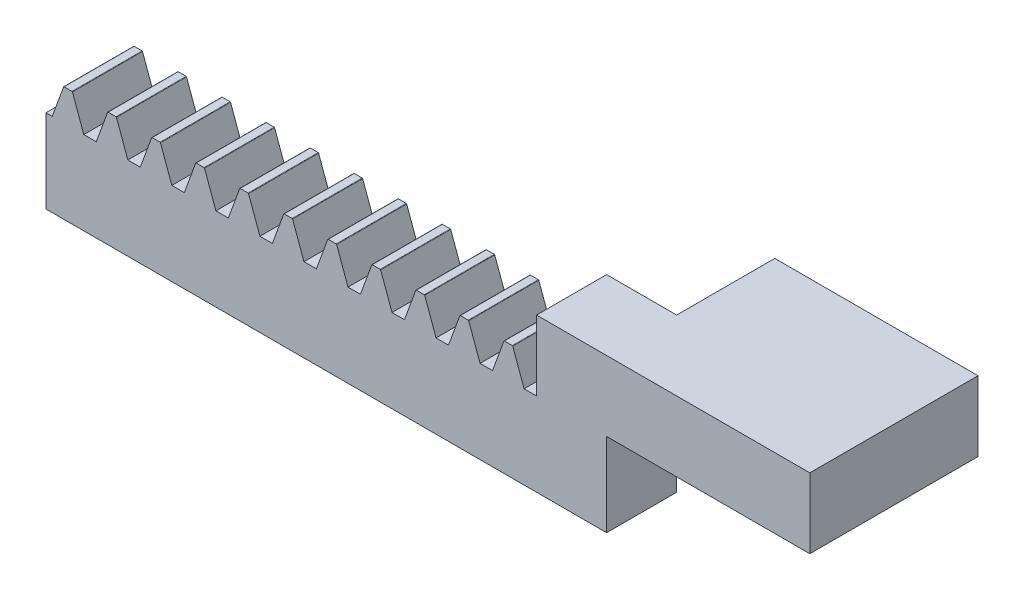
SolidWorks part; units mm, degrees
extrude "Blank" add sketch "BlankSke" against normal blind 5
sketch "BlankSke" plane through (0, 0, 0) normal (0, 0, 1) x (1, 0, 0)
  line L1 (0, 0) -> (40, 0)
  line L2 (0, 0) -> (0, 8.2)
  line L3 (0, 8.2) -> (40, 8.2)
  line L4 (40, 0) -> (40, 8.2)
  dimension "Length" = 40
ref_plane "Plane1" through (0, 0, 0) normal (0, 0, 1) x (1, 0, 0)
ref_plane "Plane2" through (0, 0, 0) normal (0, 1, 0) x (1, 0, 0)
ref_plane "Plane3" through (0, 0, 0) normal (1, 0, 0) x (0, 0, -1)
sketch "HoldingSke" plane through (0, 0, 0) normal (0, 1, 0) x (1, 0, 0)
  line L0 (0, 0) -> (0.1392, 0.9903)
  line L1 (-15, 0) -> (100, 0) construction
  line L2 (0, 0) -> (-2.1039, 2.3779)
  line L3 (0, 0) -> (-11.863, 4.5341)
  line L4 (0, 0) -> (8.3795, 2.0892)
  line L5 (0, 0) -> (-23.7986, -8.8762)
  line L6 (0, 0) -> (-10.5278, -7.1032)
  line L9 (-71.009, 38.7566) -> (-33.4213, 52.4374)
  line L10 (-76.2, 3.3779) -> (-69, 3.3779)
  line L11 (0, 0) -> (-5, 0)
  line L12 (-76.2, 101.6) -> (-76.162, 101.6)
  line L13 (24.9733, 27.94) -> (52.9518, 28.4284)
  line L14 (24.9733, 27.94) -> (24.9743, 27.94)
  line L15 (24.9733, 27.94) -> (100.4006, 29.5858)
  circle A0 centre (0, 0) radius 19.05
  circle A1 centre (0, 0) radius 3.6
  circle A2 centre (0, 0) radius 12.7
  dimension "Num_teeth" = 14
  dimension "Width" = 5
  dimension "Length" = 40
  dimension "Pitch_height" = 7.2
sketch "TooCutSkeIll" plane through (0, 0, 0) normal (0, 0, 1) x (1, 0, 0)
  line L0 (-1.2538, 8.1737) -> (-0.5045, 6.1152)
  line L1 (-0.2687, 5.95) -> (0.2687, 5.95)
  line L2 (0.5045, 6.1152) -> (1.2538, 8.1737)
  line L3 (40, 8.2) -> (0, 8.2) construction
  line L4 (0, 0) -> (0, 64.897) construction
  line L5 (-13.208, 7.2) -> (12.954, 7.2) construction
  line L6 (0, 0) -> (40, 0) construction
  line L7 (0.8994, 7.2) -> (0.8994, 48.7463) construction
  line L8 (-0.8994, 7.2) -> (-0.8994, 48.7463) construction
  line L9 (1.2914, 8.2) -> (1.2914, 8.2254)
  line L10 (-1.2914, 8.2) -> (-1.2914, 8.2254)
  line L11 (-1.2914, 8.2254) -> (1.2914, 8.2254)
  arc A0 (0.2687, 5.95) -> (0.5045, 6.1152) centre (0.2687, 6.201) ccw
  arc A1 (-0.5045, 6.1152) -> (-0.2687, 5.95) centre (-0.2687, 6.201) ccw
  arc A2 (1.2914, 8.2) -> (1.2538, 8.1737) centre (1.2914, 8.16) ccw
  arc A3 (-1.2538, 8.1737) -> (-1.2914, 8.2) centre (-1.2914, 8.16) ccw
  dimension "Addendum_plus" = 1.0254
  dimension "Pitch_height" = 7.2
  dimension "Pressure_angle" = 20
  dimension "Gap_width" = 1.7988
  dimension "Dedendum" = 1.25
extrude "ToothCutIll" cut sketch "TooCutSkeIll" against normal through all
sketch "TooCutSkeSim" plane through (0, 0, 0) normal (0, 0, 1) x (1, 0, 0)
  line L0 (0.4444, 5.95) -> (-0.4444, 5.95)
  line L1 (1.2726, 8.2254) -> (0.4444, 5.95)
  line L2 (0, 17.4625) -> (0, 53.467) construction
  line L3 (1.2726, 8.2254) -> (-1.2726, 8.2254)
  line L6 (-1.2726, 8.2254) -> (-0.4444, 5.95)
  line L9 (-0.8994, 7.2) -> (0.8994, 7.2) construction
  line L10 (0, 0) -> (40, 0) construction
  line L11 (0.8994, 7.2) -> (0.8994, 53.467) construction
  line L12 (-0.8994, 7.2) -> (-0.8994, 53.467) construction
  dimension "Addendum_plus" = 1.0254
  dimension "Pitch_height" = 7.2
  dimension "Pressure_angle" = 20
  dimension "Gap_width" = 1.7988
  dimension "Dedendum" = 1.25
extrude "ToothCutSim" cut sketch "TooCutSkeSim" against normal through all
pattern_linear "TeethCuts" count 14 spacing 3.1416 along (1, 0, 0) of "ToothCutIll", "ToothCutSim"
sketch "Sketch1" plane through (0, 0, 0) normal (0, 0, 1) x (1, 0, 0)
  line L0 (35.002, 5.95) -> (40, 5.95)
  line L1 (40, 0) -> (40, 7.0387) construction
  line L2 (40, 5.95) -> (40, 8.2)
  line L3 (40, 8.2) -> (35.002, 8.2)
  line L4 (35.002, 8.2) -> (35.002, 5.95)
extrude "Boss-Extrude1" add sketch "Sketch1" against normal blind 5
sketch "Sketch3" plane through (0, 0, 0) normal (0, 0, 1) x (1, 0, 0)
  line L1 (35.002, 5.95) -> (40, 5.95)
  line L2 (35.002, 5.95) -> (35.002, 8.2)
  line L3 (35.002, 8.2) -> (40, 8.2)
  line L4 (40, 5.95) -> (40, 8.2)
sketch "Sketch4" plane through (40, 0, 0) normal (1, 0, 0) x (0, 0, -1)
  line L1 (0, 8.2) -> (12, 8.2)
  line L2 (0, 8.2) -> (0, 5.95)
  line L3 (0, 5.95) -> (12, 5.95)
  line L4 (12, 8.2) -> (12, 5.95)
  line L7 (0, 0) -> (0, 8.2) construction
  line L8 (5, 8.2) -> (0, 8.2) construction
  line L9 (0, 0) -> (0, 8.2) construction
  point P4 (0, 0)
  point P5 (0, 8.2)
  point P7 (5.4545, 5.95)
  point P8 (0, 0)
  point P9 (0, 0)
  dimension "D1" = 12
  dimension "D2" = 2.25
extrude "Boss-Extrude4" add sketch "Sketch4" along normal blind 14.5
sketch "Sketch6" plane through (0, 8.2, 0) normal (0, 1, 0) x (1, 0, 0)
  line L10 (35.002, 5) -> (35.002, 0)
  line L24 (35.002, 5) -> (35.002, 0)
  line L34 (40, 5) -> (35.002, 5)
  line L35 (40, 5) -> (35.002, 5)
  line L57 (35.002, 0) -> (54.5, 0)
  line L59 (35.002, 0) -> (54.5, 0)
  line L61 (54.5, 0) -> (54.5, 12)
  line L62 (54.5, 0) -> (54.5, 12)
  line L63 (54.5, 12) -> (40, 12)
  line L64 (54.5, 12) -> (40, 12)
  line L65 (40, 12) -> (40, 5)
  line L66 (40, 12) -> (40, 5)
  dimension "D1" = 0
extrude "Boss-Extrude5" add sketch "Sketch6" along normal blind 2.75
ref_plane "Plane4" through (0, 0, -2.5) normal (0, 0, -1) x (-1, 0, 0)
equation "' \"Module@HoldingSke\" = 6.35"
equation "' \"Num_teeth@HoldingSke\" = 12"
equation "' \"Ap@HoldingSke\" =  20"
equation "' \"Ap@HoldingSke\" = 20"
equation "' \"Width@HoldingSke\" = 0.25 * 25.4"
equation "' \"Show_teeth@HoldingSke\" = 500"
equation "' \"Backlash@HoldingSke\" = 0.009 * 25.4"
equation "' \"Addendum_fac@HoldingSke\" = 1.0"
equation "' \"Dedendum_fac@HoldingSke\" = 1.25"
equation "' \"Dedendum_add@HoldingSke\" = 0.00005 * 25.4"
equation "' \"Clearance_fac@HoldingSke\" = 0.25"
equation "' \"Pitch_height@HoldingSke\" = 1 * 25.4"
equation "' \"Length@HoldingSke\" = 4.71 * 25.4"
equation "\"Pitch@HoldingSke\" = 1 / \"Module@HoldingSke\""
equation "\"MPH@HoldingSke\" = \"Dedendum_fac@HoldingSke\" / \"Pitch@HoldingSke\" + 2 * \"Dedendum_add@HoldingSke\" + 0.002 * 25.4"
equation "\"MPH@HoldingSke\" = ((sgn( \"MPH@HoldingSke\" - \"Pitch_height@HoldingSke\")+1)*( \"MPH@HoldingSke\" - \"Pitch_height@HoldingSke\"))/2 + \"Pitch_height@HoldingSke\""
equation "\"Blank_height@BlankSke\" = \"Pitch_height@HoldingSke\" + \"Addendum_fac@HoldingSke\"  / \"Pitch@HoldingSke\" "
equation "\"Length@BlankSke\" =  \"Length@HoldingSke\""
equation "\"Face_width@Blank\" = \"Width@HoldingSke\""
equation "\"Pressure_angle@TooCutSkeIll\" = \"Ap@HoldingSke\""
equation "\"Addendum_plus@TooCutSkeIll\" =  \"Addendum_fac@HoldingSke\"  / \"Pitch@HoldingSke\" + 0.001 *25.4"
equation "\"Dedendum@TooCutSkeIll\" = \"Dedendum_fac@HoldingSke\"  / \"Pitch@HoldingSke\""
equation "\"Pitch_height@TooCutSkeIll\" =  \"MPH@HoldingSke\""
equation "\"Gap_width@TooCutSkeIll\" = 3.14159265 / 2 / \"Pitch@HoldingSke\" + 6 * \"Backlash@HoldingSke\""
equation "\"Pressure_angle@TooCutSkeSim\" = \"Ap@HoldingSke\""
equation "\"Addendum_plus@TooCutSkeSim\" =  \"Addendum_fac@HoldingSke\"  / \"Pitch@HoldingSke\" + 0.001 * 25.4"
equation "\"Dedendum@TooCutSkeSim\" = \"Dedendum_fac@HoldingSke\"  / \"Pitch@HoldingSke\""
equation "\"Pitch_height@TooCutSkeSim\" =  \"MPH@HoldingSke\""
equation "\"Gap_width@TooCutSkeSim\" = 3.14159265 / 2 / \"Pitch@HoldingSke\" + 6 * \"Backlash@HoldingSke\""
equation "\"Root_fillet@TooCutSkeIll\" = \"Clearance_fac@HoldingSke\" / \"Pitch@HoldingSke\" + \"Dedendum_add@HoldingSke\""
equation "\"Break_rad@TooCutSkeIll\" = 0.02 / \"Pitch@HoldingSke\" * 2"
equation "\"Linear_pitch@TeethCuts\" = 3.14159265 / \"Pitch@HoldingSke\""
equation "\"Num_teeth@HoldingSke\" = int( ( \"Length@HoldingSke\" + 0 ) / (3.14159265 / \"Pitch@HoldingSke\")) + 0.9999  + 1"
equation " \"Num_teeth@TeethCuts\" = int( \"Show_teeth@HoldingSke\" ) + 1"
equation " \"Num_teeth@TeethCuts\" = ((sgn( \"Num_teeth@TeethCuts\" - \"Num_teeth@HoldingSke\" )-1)*( \"Num_teeth@TeethCuts\" - \"Num_teeth@HoldingSke\" ))/-2+ \"Num_teeth@HoldingSke\""
equation " \"Num_teeth@TeethCuts\" = ((sgn( \"Num_teeth@TeethCuts\" - 2.0)+1)*( \"Num_teeth@TeethCuts\" - 2.0))/2 +2.0"
